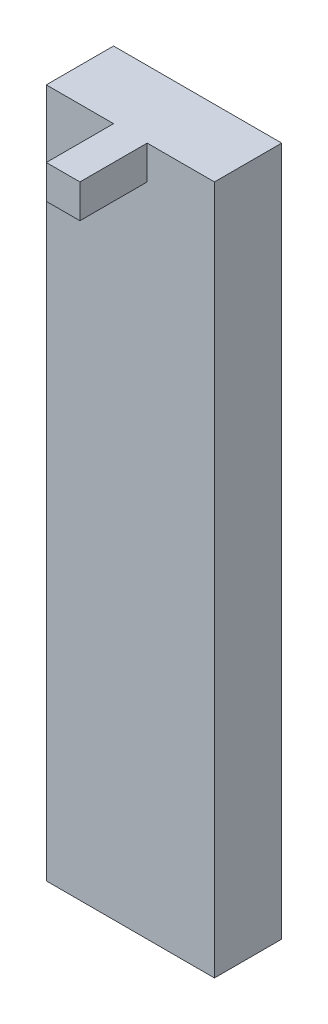
SolidWorks part; units mm, degrees
material "ABS"
ref_plane "Front" through (0, 0, 0) normal (0, 0, 1) x (1, 0, 0)
ref_plane "Top" through (0, 0, 0) normal (0, 1, 0) x (1, 0, 0)
ref_plane "Right" through (0, 0, 0) normal (1, 0, 0) x (0, 0, -1)
sketch "Sketch1" plane through (0, 0, 0) normal (0, 0, 1) x (1, 0, 0)
  line L0 (-12.5, 5.1586) -> (-12.5, 108.2095) construction
  line L1 (0, 0) -> (-25, 0)
  line L2 (0, 0) -> (0, 102.5)
  line L3 (0, 102.5) -> (-25, 102.5)
  line L4 (-25, 0) -> (-25, 102.5)
  line L5 (-15, 102.5) -> (-10, 102.5)
  line L6 (-15, 102.5) -> (-15, 97.5)
  line L7 (-15, 97.5) -> (-10, 97.5)
  line L8 (-10, 102.5) -> (-10, 97.5)
  line L9 (-15, 102.5) -> (-10, 97.5) construction
  line L10 (-15, 97.5) -> (-10, 102.5) construction
  point P5 (-12.5, 100)
  dimension "D1" = 25
  dimension "D2" = 5
  dimension "D3" = 5
  dimension "D4" = 100
extrude "Boss-Extrude1" add sketch "Sketch1" along normal blind 10 contours L3 L8 L7 L6 L4 L1 L2 region at (-12.5, 50.7697, 0)
extrude "Boss-Extrude2" add sketch "Sketch1<3>" along normal blind 20 contours L6 L7 L8 L5
sketch "Sketch1<3>" plane through (0, 0, 0) normal (0, 0, 1) x (1, 0, 0) same geometry as "Sketch1"
